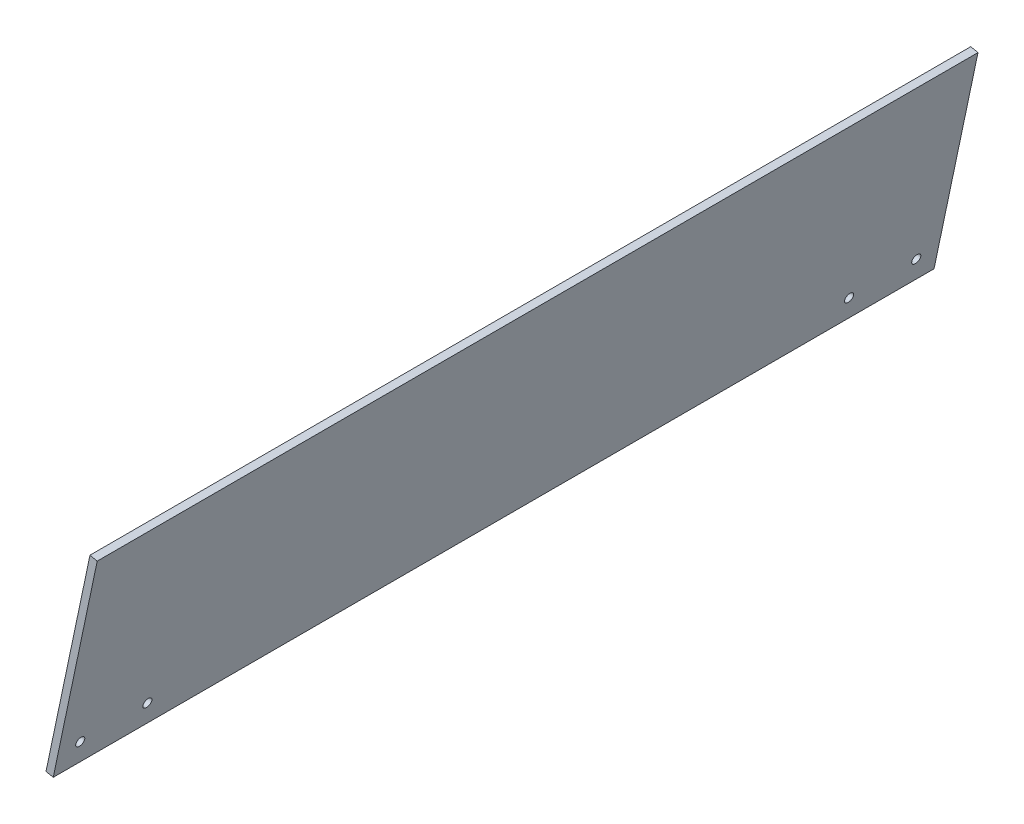
SolidWorks part; units mm, degrees
ref_plane "Front Plane" through (0, 0, 0) normal (0, 0, 1) x (1, 0, 0)
ref_plane "Top Plane" through (0, 0, 0) normal (0, 1, 0) x (1, 0, 0)
ref_plane "Right Plane" through (0, 0, 0) normal (1, 0, 0) x (0, 0, -1)
sketch "Sketch1" plane through (0, 0, 0) normal (0, 0, 1) x (1, 0, 0)
  line L0 (24.224, -184.5309) -> (43.8641, -91.066)
  line L1 (74.6326, -84.2378) -> (-36.1779, -321.8717) construction
  line L2 (24.224, -184.5309) -> (27.4535, -185.2095)
  line L3 (27.4535, -185.2095) -> (47.0936, -91.7446)
  line L4 (47.0936, -91.7446) -> (43.8641, -91.066)
  circle A1 centre (53.023, -69.9683) radius 17.5 construction
  dimension "D1" = 25
  dimension "D2" = 23
  dimension "D3" = 3.3
extrude "Boss-Extrude1" add sketch "Sketch1" along normal up to surface (393.4 mm away)
sketch "Sketch2" plane through (60.3359, -12.6786, 0) normal (-0.9786, 0.2056, 0) x (0, 0, 1)
  circle A0 centre (383.4, -165.6055) radius 2
  circle A1 centre (353.4, -165.6055) radius 2
  circle A2 centre (40, -165.6055) radius 2
  circle A3 centre (10, -165.6055) radius 2
  dimension "D1" = 4
  dimension "D2" = 4
  dimension "D3" = 4
  dimension "D4" = 4
extrude "Cut-Extrude1" cut sketch "Sketch2" against normal blind 4
